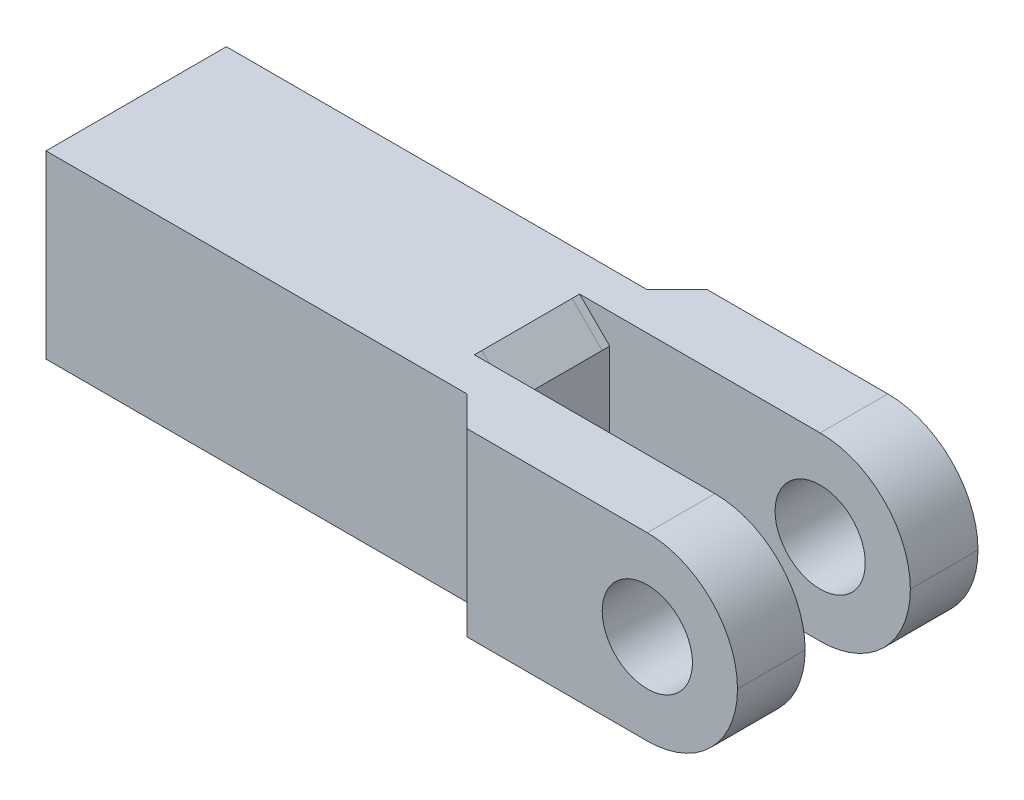
SolidWorks part; units mm, degrees
material "PBT General Purpose"
ref_plane "Front Plane" through (0, 0, 0) normal (0, 0, 1) x (1, 0, 0)
ref_plane "Top Plane" through (0, 0, 0) normal (0, 1, 0) x (1, 0, 0)
ref_plane "Right Plane" through (0, 0, 0) normal (1, 0, 0) x (0, 0, -1)
sketch "Sketch1" plane through (0, 0, 0) normal (1, 0, 0) x (0, 0, -1)
  line L1 (-3, 3) -> (3, 3)
  line L2 (-3, 3) -> (-3, -3)
  line L3 (-3, -3) -> (3, -3)
  line L4 (3, 3) -> (3, -3)
  line L5 (-3, 3) -> (3, -3) construction
  line L6 (-3, -3) -> (3, 3) construction
  point P0 (0, 0)
  dimension "D1" = 6
  dimension "D2" = 6
extrude "Boss-Extrude1" add sketch "Sketch1" along normal blind 14
sketch "Sketch2" plane through (14, 0, 0) normal (1, 0, 0) x (0, 0, -1)
  line L0 (-3, -3) -> (3, -3) construction
  line L1 (-1.5, 3) -> (1.5, 3)
  line L2 (-1.5, 3) -> (-1.5, -3)
  line L3 (-1.5, -3) -> (1.5, -3)
  line L4 (1.5, 3) -> (1.5, -3)
  line L5 (-1.5, 3) -> (1.5, -3) construction
  line L6 (-1.5, -3) -> (1.5, 3) construction
  line L7 (1.5, 3) -> (1.5, -3)
  line L8 (4, -3) -> (4, 3)
  line L9 (4, 3) -> (1.5, 3)
  line L10 (1.5, -3) -> (4, -3)
  point P0 (0, 0)
  line M3 (3, -3) -> (3, 3)
  line M4 (3, 3) -> (-3, 3)
  line M6 (-3, -3) -> (3, -3)
  dimension "D1" = 3
  dimension "D2" = 2.5
extrude "Boss-Extrude2" add sketch "Sketch2" along normal blind 10 contours L10 L8 L9 M3 | L4 M4 M6 M3 region at (14, 0, -2.25) region at (14, 0, -3.5)
fillet "Fillet1" radius 3 2 edges at (24, -3, -2.75) (24, 3, -2.75)
sketch "Sketch3" plane through (0, 0, -4) normal (0, 0, -1) x (-1, 0, 0)
  circle A0 centre (-21, 0) radius 1.5
  arc A1 (-21, 3) -> (-24, 0) centre (-21, 0) ccw construction
  dimension "D1" = 3
extrude "Cut-Extrude1" cut sketch "Sketch3" against normal blind 10
chamfer "Chamfer1" distance 1 angle 45 1 edges at (14, 0, -4)
chamfer "Chamfer2" distance 1 angle 45 2 edges at (14, -3, 0.75) (14, 3, 0.75)
ref_plane "Plane1" through (0, 0, 0) normal (0, 0, -1) x (-1, 0, 0)
mirror "Mirror2" about plane through (0, 0, 0) normal (0, 0, -1) of "Boss-Extrude1", "Fillet1", "Cut-Extrude1", "Boss-Extrude2", "Chamfer1"
sketch "Sketch4" plane through (0, 0, 0) normal (-1, 0, 0) x (0, 0, 1)
  circle A0 centre (0, 0) radius 1.25
  dimension "D1" = 2.5
extrude "Cut-Extrude2" cut sketch "Sketch4" against normal blind 13
cosmetic thread "Cosmetic Thread1" parameters "D2"=3
chamfer "Chamfer3" distance 1 angle 45 2 edges at (14, 3, 0) (14, -3, 0)
sketch "Sketch5" plane through (0, 0, 0) normal (0, 1, 0) x (1, 0, 0)
  line L0 (24, -1.5) -> (24, -4) construction
  line L1 (14, -1.5) -> (24, -1.5)
  line L2 (14, -1.5) -> (14, -1.75)
  line L3 (14, -1.75) -> (24, -1.75)
  line L4 (24, -1.5) -> (24, -1.75)
  dimension "D1" = 0.25
extrude "Cut-Extrude3" cut sketch "Sketch5" against normal blind 10 and the other way blind 10
sketch "Sketch6" plane through (0, 0, 0) normal (0, 1, 0) x (1, 0, 0)
  line L0 (24, 4) -> (24, 1.5) construction
  line L1 (14, 1.5) -> (24, 1.5)
  line L2 (14, 1.5) -> (14, 1.75)
  line L3 (14, 1.75) -> (24, 1.75)
  line L4 (24, 1.5) -> (24, 1.75)
  dimension "D1" = 0.25
extrude "Cut-Extrude4" cut sketch "Sketch6" against normal blind 10 and the other way blind 10
chamfer "Chamfer4" distance 1 angle 45 4 edges at (14, -3, 1.625) (14, -3, -1.625) (14, 3, -1.625) (14, 3, 1.625)
